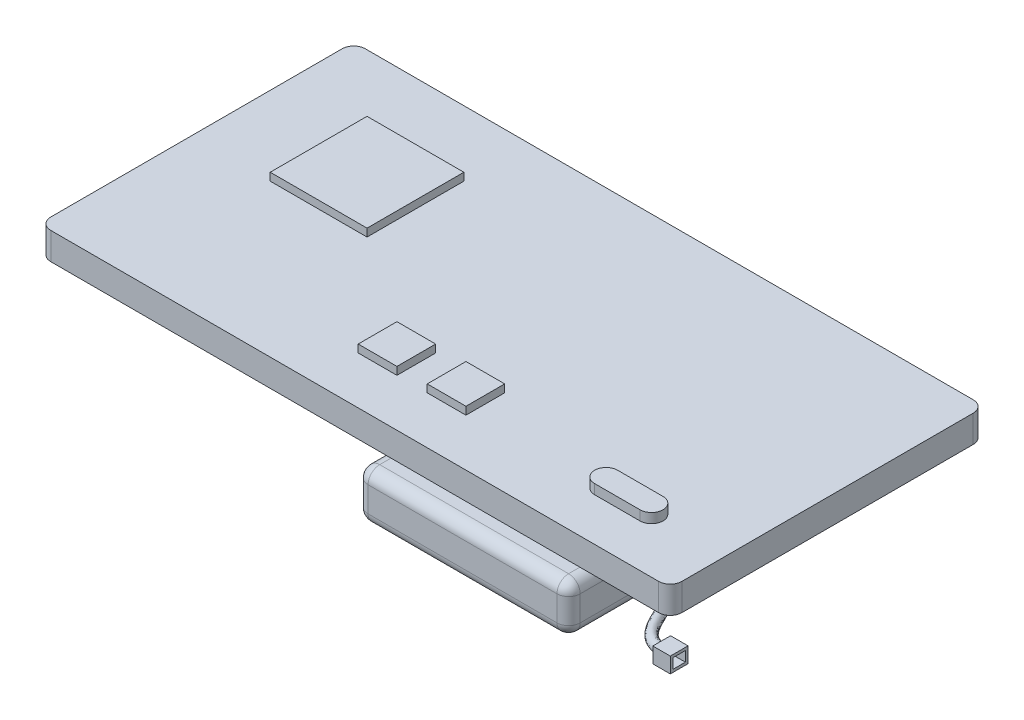
SolidWorks part; units mm, degrees
ref_plane "前视基准面" through (0, 0, 0) normal (0, 0, 1) x (1, 0, 0)
ref_plane "上视基准面" through (0, 0, 0) normal (0, 1, 0) x (1, 0, 0)
ref_plane "右视基准面" through (0, 0, 0) normal (1, 0, 0) x (0, 0, -1)
sketch "草图1" plane through (0, 0, 0) normal (0, 1, 0) x (1, 0, 0)
  line L1 (-81.4812, -40.6121) -> (81.4812, -40.6121)
  line L2 (-81.4812, -40.6121) -> (-81.4812, 40.6121)
  line L3 (-81.4812, 40.6121) -> (81.4812, 40.6121)
  line L4 (81.4812, -40.6121) -> (81.4812, 40.6121)
  line L5 (-81.4812, -40.6121) -> (81.4812, 40.6121) construction
  line L6 (-81.4812, 40.6121) -> (81.4812, -40.6121) construction
  point P0 (0, 0)
extrude "凸台-拉伸1" add sketch "草图1" along normal blind 7
sketch "草图2" plane through (0, 7, 0) normal (0, 1, 0) x (1, 0, 0)
  line L1 (-61.159, -1.2706) -> (-36.159, -1.2706)
  line L2 (-61.159, -1.2706) -> (-61.159, 23.7294)
  line L3 (-61.159, 23.7294) -> (-36.159, 23.7294)
  line L4 (-36.159, -1.2706) -> (-36.159, 23.7294)
  line L5 (-61.159, -1.2706) -> (-36.159, 23.7294) construction
  line L6 (-61.159, 23.7294) -> (-36.159, -1.2706) construction
  line L7 (-11.3813, -18.3321) -> (-1.3813, -18.3321)
  line L8 (-11.3813, -18.3321) -> (-11.3813, -28.3321)
  line L9 (-11.3813, -28.3321) -> (-1.3813, -28.3321)
  line L10 (-1.3813, -18.3321) -> (-1.3813, -28.3321)
  line L11 (-11.3813, -18.3321) -> (-1.3813, -28.3321) construction
  line L12 (-11.3813, -28.3321) -> (-1.3813, -18.3321) construction
  line L13 (6.4423, -28.3321) -> (16.4423, -28.3321)
  line L14 (6.4423, -28.3321) -> (6.4423, -18.3321)
  line L15 (6.4423, -18.3321) -> (16.4423, -18.3321)
  line L16 (16.4423, -28.3321) -> (16.4423, -18.3321)
  line L17 (6.4423, -28.3321) -> (16.4423, -18.3321) construction
  line L18 (6.4423, -18.3321) -> (16.4423, -28.3321) construction
  point P0 (-48.659, 11.2294)
  point P5 (-6.3813, -23.3321)
  point P10 (11.4423, -23.3321)
  dimension "D1" = 10
  dimension "D2" = 10
  dimension "D3" = 10
  dimension "D4" = 25
  dimension "D5" = 25
extrude "凸台-拉伸2" add sketch "草图2" along normal blind 2
sketch "草图3" plane through (0, 7, 0) normal (0, 1, 0) x (1, 0, 0)
  line L0 (50.835, -26.5332) -> (62.5616, -26.5332) construction
  line L1 (50.835, -23.5565) -> (62.5616, -23.5565)
  line L2 (50.835, -29.51) -> (62.5616, -29.51)
  arc A0 (50.835, -23.5565) -> (50.835, -29.51) centre (50.835, -26.5332) ccw
  arc A1 (62.5616, -29.51) -> (62.5616, -23.5565) centre (62.5616, -26.5332) ccw
  point P2 (56.6983, -26.5332)
extrude "凸台-拉伸3" add sketch "草图3" along normal blind 2.5
fillet "圆角1" radius 3 4 edges at (-81.4812, 3.5, -40.6121) (81.4812, 3.5, -40.6121) (81.4812, 3.5, 40.6121) (-81.4812, 3.5, 40.6121)
ref_plane "基准面1" through (0, -40, 0) normal (0, 1, 0) x (1, 0, 0)
sketch "草图4" plane through (0, -40, 0) normal (0, 1, 0) x (1, 0, 0)
  line L1 (-27.3899, -12.7754) -> (27.3899, -12.7754)
  line L2 (-27.3899, -12.7754) -> (-27.3899, 12.7754)
  line L3 (-27.3899, 12.7754) -> (27.3899, 12.7754)
  line L4 (27.3899, -12.7754) -> (27.3899, 12.7754)
  line L5 (-27.3899, -12.7754) -> (27.3899, 12.7754) construction
  line L6 (-27.3899, 12.7754) -> (27.3899, -12.7754) construction
  point P0 (0, 0)
extrude "凸台-拉伸4" add sketch "草图4" along normal mid plane 12.5 separate body
sketch "草图5" plane through (27.3899, 0, 0) normal (1, 0, 0) x (0, 0, -1)
  line L0 (44.6733, -40) -> (-44.6733, -40) construction
  line L1 (3.8688, -42.0166) -> (7.9736, -42.0166)
  line L2 (3.8688, -42.0166) -> (3.8688, -37.9834)
  line L3 (3.8688, -37.9834) -> (7.9736, -37.9834)
  line L4 (7.9736, -42.0166) -> (7.9736, -37.9834)
  line L5 (3.8688, -42.0166) -> (7.9736, -37.9834) construction
  line L6 (3.8688, -37.9834) -> (7.9736, -42.0166) construction
  point P0 (5.9212, -40)
extrude "凸台-拉伸5" add sketch "草图5" along normal blind 1.5
ref_plane "基准面2" through (0, 0, -6) normal (0, 0, 1) x (1, 0, 0)
sketch "草图8" plane through (28.8899, 0, 0) normal (1, 0, 0) x (0, 0, -1)
  line L0 (6, 30.6625) -> (6, -30.6625) construction
  line L1 (44.6733, -40) -> (-44.6733, -40) construction
  circle A0 centre (6, -40) radius 1.25
  dimension "D1" = 2.5
sketch "草图6" plane through (0, -40, 0) normal (0, 1, 0) x (1, 0, 0)
  line L0 (-30.6625, 6) -> (30.6625, 6) construction
  spline S0 degree 3 poles (28.8899, 6) (40.8433, 8.1308) (37.3719, -9.0099) (47.9322, -8.4888) knots 0 0 0 0 1 1 1 1
  point P2 (28.8899, 6)
sweep "扫描2" add profiles "草图8" path "草图6"
sketch "草图9" plane through (0, -40, 0) normal (0, 1, 0) x (1, 0, 0)
  line L1 (51.6945, -6.2346) -> (47.1732, -6.2346)
  line L2 (51.6945, -6.2346) -> (51.6945, -10.8192)
  line L3 (51.6945, -10.8192) -> (47.1732, -10.8192)
  line L4 (47.1732, -6.2346) -> (47.1732, -10.8192)
  line L5 (51.6945, -6.2346) -> (47.1732, -10.8192) construction
  line L6 (51.6945, -10.8192) -> (47.1732, -6.2346) construction
  point P0 (49.4339, -8.5269)
extrude "凸台-拉伸6" add sketch "草图9" along normal mid plane 4
sketch "草图10" plane through (51.6945, 0, 0) normal (1, 0, 0) x (0, 0, -1)
  line L8 (-10.1192, -41.3) -> (-6.9346, -41.3)
  line L9 (-6.9346, -41.3) -> (-6.9346, -38.7)
  line L10 (-6.9346, -38.7) -> (-10.1192, -38.7)
  line L11 (-10.1192, -38.7) -> (-10.1192, -41.3)
  line L12 (-10.1192, -41.3) -> (-6.9346, -41.3)
  line L13 (-6.9346, -41.3) -> (-6.9346, -38.7)
  line L14 (-6.9346, -38.7) -> (-10.1192, -38.7)
  line L15 (-10.1192, -38.7) -> (-10.1192, -41.3)
  dimension "D1" = 0.7
extrude "切除-拉伸1" cut sketch "草图10" against normal blind 3.5
fillet "圆角2" radius 3 12 edges at (27.3899, -40, -12.7754) (0, -33.75, -12.7754) (0, -46.25, -12.7754) (27.3899, -46.25, 0) (27.3899, -33.75, 0) (27.3899, -40, 12.7754) (0, -46.25, 12.7754) (0, -33.75, 12.7754) (-27.3899, -46.25, 0) (-27.3899, -40, -12.7754) (-27.3899, -33.75, 0) (-27.3899, -40, 12.7754)
